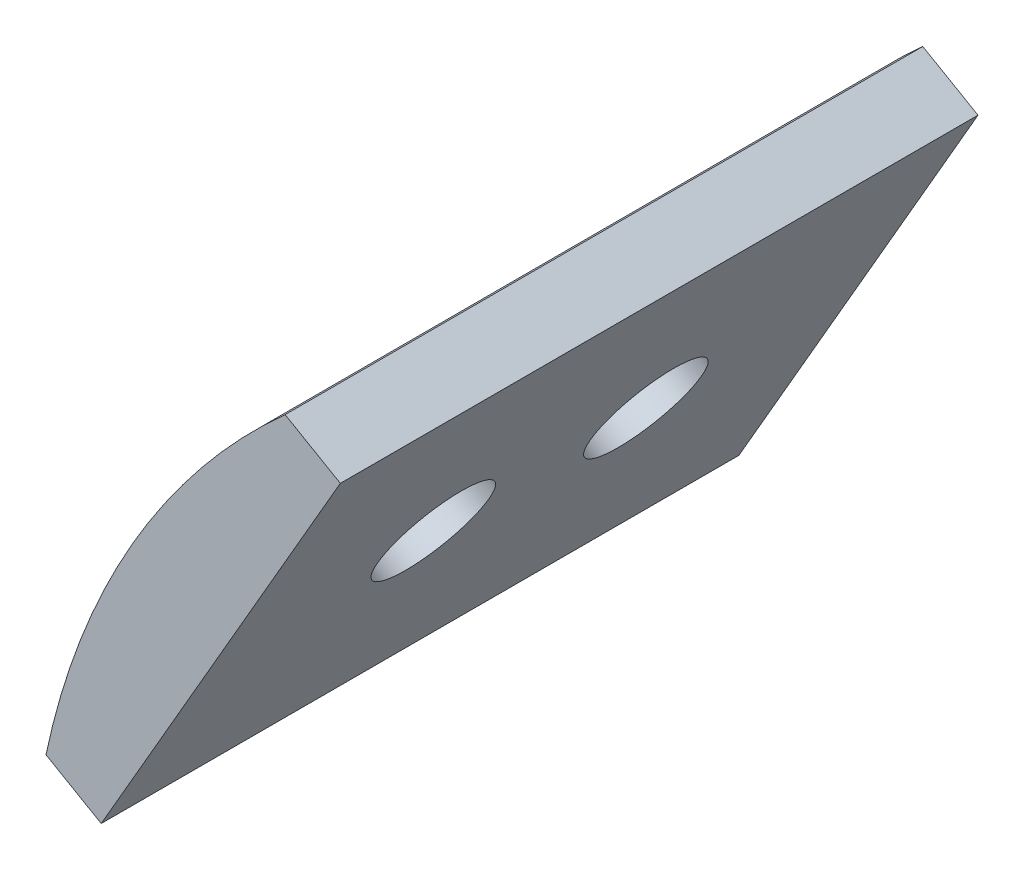
SolidWorks part; units mm, degrees
other "Videocamera1"
material "PET"
ref_plane "Piano frontale" through (0, 0, 0) normal (0, 0, 1) x (1, 0, 0)
ref_plane "Piano superiore" through (0, 0, 0) normal (0, 1, 0) x (1, 0, 0)
ref_plane "Piano destro" through (0, 0, 0) normal (1, 0, 0) x (0, 0, -1)
sketch "Schizzo2" plane through (0, 0, 0) normal (0, 0, 1) x (1, 0, 0)
  line L0 (0, 15) -> (0, 0)
  line L1 (0, 0) -> (-12.9904, -7.5)
  line L2 (0, 0) -> (12.9904, -7.5)
  line L3 (-7.5, 12.9904) -> (-15, 0)
  line L4 (-1, 15) -> (-1, 0)
  line L5 (-0.5, 0.866) -> (-13.4904, -6.634)
  line L6 (-15, 0) -> (-8.5, -3.7528)
  line L7 (-7.5, 12.9904) -> (-1, 9.2376)
  line L8 (-7.5, 12.9904) -> (-5.7679, 11.9904)
  line L9 (-7.5, 12.9904) -> (-15.0077, -0.0133)
  line L10 (-5.7679, 11.9904) -> (-13.2756, -1.0133)
  line L11 (-15.0077, -0.0133) -> (-13.2756, -1.0133)
  circle A0 centre (0, 0) radius 15
  circle A1 centre (8.6076, -4.9696) radius 24.125
  dimension "D1" = 30
  dimension "D6" = 48.25
  dimension "D2" = 120
  dimension "D3" = 120
  dimension "D4" = 15
  dimension "D7" = 2
  dimension "D5" = 1
extrude "Estrusione-Estrusione1" add sketch "Schizzo2" along normal blind 20 contours L10 L7 L3 L6 | L3 A1 region at (-10.384, 5.9952, 0) region at (-11.665, 6.7348, 0)
ref_plane "Piano4" through (-12.2853, 7.0929, 0) normal (-0.866, 0.5, 0) x (0, 0, 1)
sketch "Schizzo3" plane through (-12.2853, 7.0929, 0) normal (-0.866, 0.5, 0) x (0, 0, 1)
  line L0 (0, 0) -> (6.6667, 0) construction
  line L1 (6.6667, 0) -> (13.3333, 0) construction
  line L2 (13.3333, 0) -> (20, 0) construction
  line L6 (0, 7.5) -> (0, -7.5)
  line L7 (0, -7.5) -> (20, -7.5)
  line L8 (20, -7.5) -> (20, 7.5)
  line L9 (20, 7.5) -> (0, 7.5)
  line L10 (0, 7.5) -> (0, -7.5)
  line L11 (0, -7.5) -> (20, -7.5)
  line L12 (20, -7.5) -> (20, 7.5)
  line L13 (20, 7.5) -> (0, 7.5)
  circle A0 centre (6.6667, 0) radius 3.15
  circle A1 centre (13.3333, 0) radius 3.15
  circle A2 centre (6.6667, 0) radius 1.75
  circle A3 centre (13.3333, 0) radius 1.75
  point P10 (6.6667, 0)
  point P11 (13.3333, 0)
  dimension "D2" = 3.5
  dimension "D3" = 6.3
  dimension "D1" = 0
extrude "Taglio-Estrusione1" cut sketch "Schizzo3" against normal through all contours A2 | A3 region at (-12.2853, 7.0929, 6.6667) region at (-12.2853, 7.0929, 13.3333)
extrude "Taglio-Estrusione2" cut sketch "Schizzo3<3>" against normal blind 1 contours A0 A2 | A1 A3 region at (-12.2853, 7.0929, 3.6058) region at (-12.2853, 7.0929, 10.2724)
sketch "Schizzo3<3>" plane through (-12.2853, 7.0929, 0) normal (-0.866, 0.5, 0) x (0, 0, 1) same geometry as "Schizzo3"
chamfer "Smusso2" distance 1.3 angle 45 2 edges at (-12.2942, 5.0774, 6.6667) (-12.2942, 5.0774, 13.3333)
